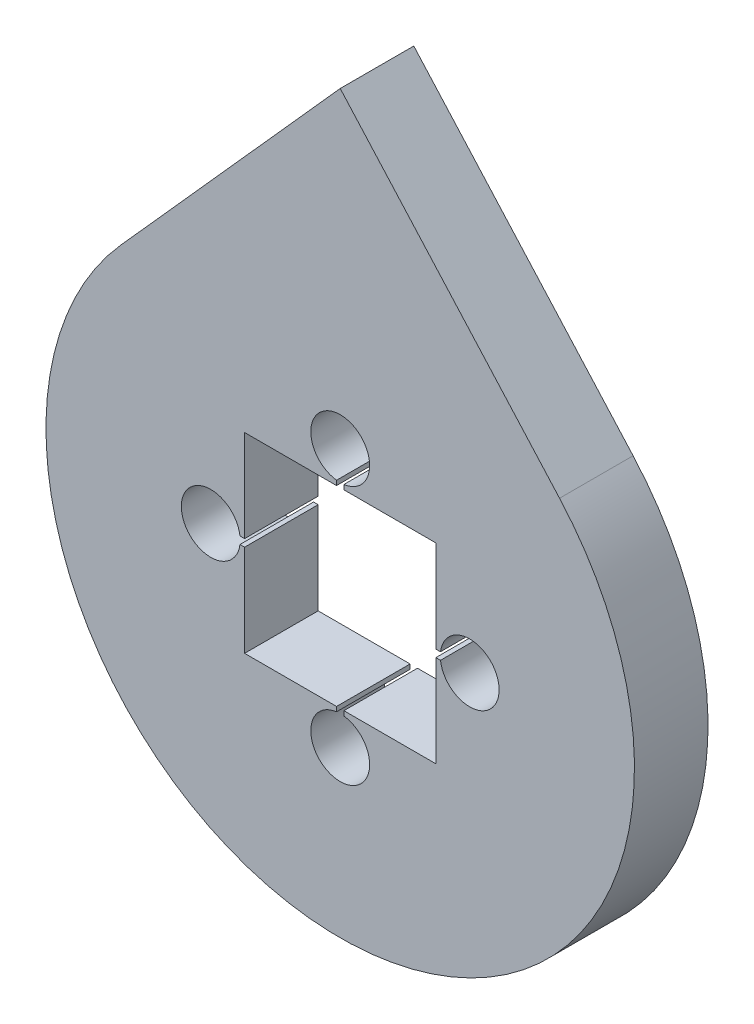
SolidWorks part; units mm, degrees
ref_plane "Front Plane" through (0, 0, 0) normal (0, 0, 1) x (1, 0, 0)
ref_plane "Top Plane" through (0, 0, 0) normal (0, 1, 0) x (1, 0, 0)
ref_plane "Right Plane" through (0, 0, 0) normal (1, 0, 0) x (0, 0, -1)
sketch "Sketch1" plane through (0, 0, 0) normal (0, 0, 1) x (1, 0, 0)
  line L0 (-11.176, 0) -> (0, 0) construction
  line L1 (-8.255, 8.255) -> (8.255, 8.255)
  line L2 (-8.255, 8.255) -> (-8.255, -8.255)
  line L3 (-8.255, -8.255) -> (8.255, -8.255)
  line L4 (8.255, 8.255) -> (8.255, -8.255)
  line L5 (0, 0) -> (0, 11.176) construction
  line L6 (11.176, 0) -> (0, 0) construction
  line L7 (0, 0) -> (0, -11.176) construction
  line L9 (-8.6559, 0.3175) -> (8.6559, 0.3175)
  line L10 (-8.6559, 0.3175) -> (-8.6559, -0.3175)
  line L11 (-8.6559, -0.3175) -> (8.6559, -0.3175)
  line L12 (8.6559, 0.3175) -> (8.6559, -0.3175)
  line L13 (-0.3175, 8.6559) -> (0.3175, 8.6559)
  line L14 (-0.3175, 8.6559) -> (-0.3175, -8.6559)
  line L15 (-0.3175, -8.6559) -> (0.3175, -8.6559)
  line L16 (0.3175, 8.6559) -> (0.3175, -8.6559)
  circle A0 centre (0, 0) radius 25.4
  circle A1 centre (0, 11.176) radius 2.54
  circle A2 centre (0, -11.176) radius 2.54
  circle A3 centre (11.176, 0) radius 2.54
  circle A4 centre (-11.176, 0) radius 2.54
  point P7 (8.255, 0)
  point P8 (0, 8.255)
  point P21 (0, 0)
  dimension "D2" = 50.8
  dimension "D4" = 5.08
  dimension "D1" = 16.51
  dimension "D3" = 11.176
  dimension "D5" = 0.635
extrude "Boss-Extrude1" add sketch "Sketch1" along normal blind 6.35 contours A0 A4 L9 L2 L1 L14 A1 L16 L4 A3 L11 L3 A2 region at (-24.6816, 0, 0)
sketch "Sketch2" plane through (0, 0, 6.35) normal (0, 0, 1) x (1, 0, 0)
  line L0 (-18.932, 16.9333) -> (0, 38.1)
  line L1 (0, 38.1) -> (18.932, 16.9333)
  circle A0 centre (0, 0) radius 25.4 construction
  circle A1 centre (0, 0) radius 25.4
  point P4 (0, 0)
  point P6 (0, 42.3086)
  circle M23 centre (0, 0) radius 25.4
  dimension "D1" = 38.1
extrude "Boss-Extrude2" add sketch "Sketch2" against normal up to surface (6.35 mm away) contours L1 L0 M23 region at (0, 28.4814, 6.35) up to face at (0, 0, 0)
